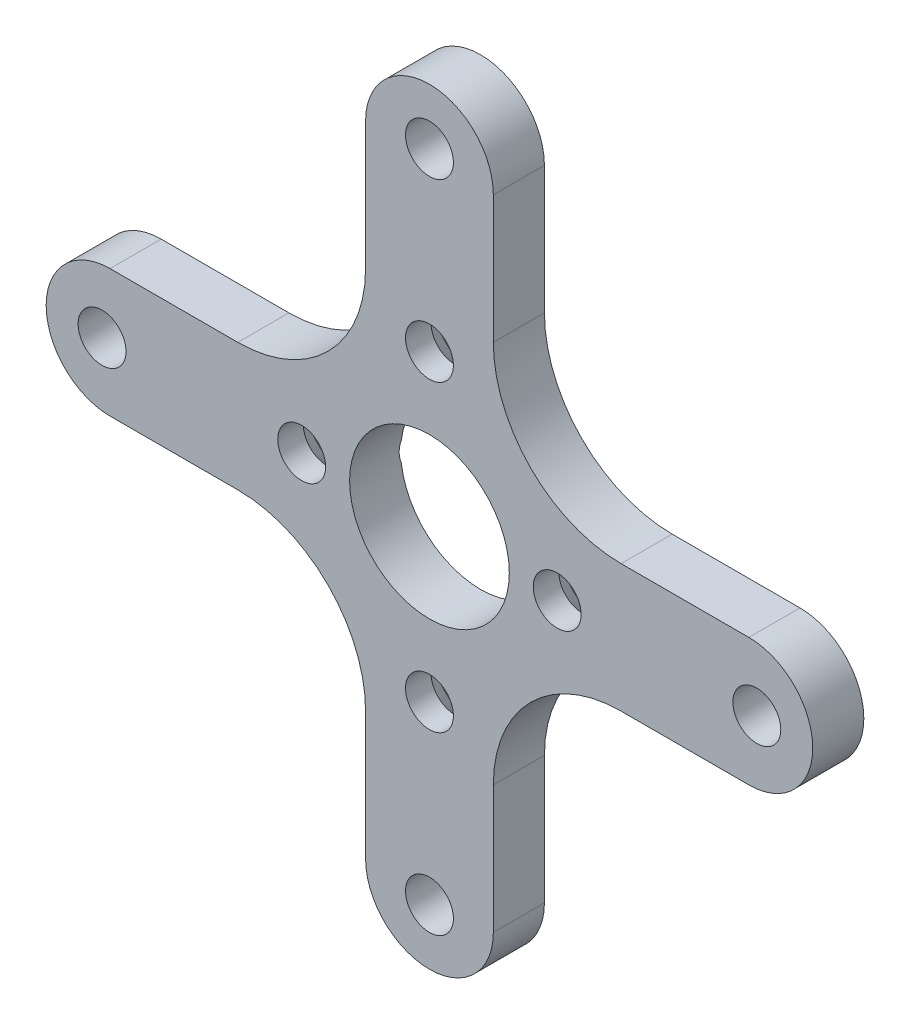
SolidWorks part; units mm, degrees
ref_plane "Спереди" through (0, 0, 0) normal (0, 0, 1) x (1, 0, 0)
ref_plane "Сверху" through (0, 0, 0) normal (0, 1, 0) x (1, 0, 0)
ref_plane "Справа" through (0, 0, 0) normal (1, 0, 0) x (0, 0, -1)
sketch "Эскиз1" plane through (0, 0, 0) normal (0, 0, 1) x (1, 0, 0)
  line L0 (-4, 20) -> (-4, 12)
  line L1 (-12, 4) -> (-20, 4)
  line L2 (-20, -4) -> (-12, -4)
  line L3 (-4, -12) -> (-4, -20)
  line L4 (4, -20) -> (4, -12)
  line L5 (12, -4) -> (20, -4)
  line L6 (4, 20) -> (4, 12)
  line L7 (12, 4) -> (20, 4)
  arc A0 (-4, 20) -> (4, 20) centre (0, 20) cw
  arc A1 (-4, 12) -> (-12, 4) centre (-12, 12) cw
  arc A2 (-20, 4) -> (-20, -4) centre (-20, 0) ccw
  arc A4 (-4, -20) -> (4, -20) centre (0, -20) ccw
  arc A5 (4, -12) -> (12, -4) centre (12, -12) cw
  arc A6 (4, 12) -> (12, 4) centre (12, 12) ccw
  arc A7 (20, 4) -> (20, -4) centre (20, 0) cw
  arc A8 (-12, -4) -> (-4, -12) centre (-12, -12) cw
  circle A13 centre (0, 0) radius 5
  circle A14 centre (0, 0) radius 8 construction
  circle A15 centre (0, 0) radius 9.5 construction
  circle A16 centre (0, 9.5) radius 1.5
  circle A17 centre (0, -9.5) radius 1.5
  circle A18 centre (-8, 0) radius 1.5
  circle A19 centre (8, 0) radius 1.5
  circle A20 centre (0, 0) radius 24 construction
  circle A22 centre (0, 20.5) radius 1.5
  circle A23 centre (20.5, 0) radius 1.5
  circle A24 centre (-20.5, 0) radius 1.5
  circle A25 centre (0, -20.5) radius 1.5
  circle A26 centre (0, 0) radius 20.5 construction
  dimension "D2" = 3
  dimension "D3" = 10
  dimension "D4" = 16
  dimension "D5" = 19
  dimension "D6" = 48
  dimension "D7" = 41
  dimension "D8" = 8
  dimension "D1" = 8
extrude "Бобышка-Вытянуть1" add sketch "Эскиз1" along normal blind 3.2
chamfer "Фаска1" distance 1.6 angle 45 4 edges at (1.5, -9.5, 0) (1.5, 9.5, 0) (-6.5, 0, 0) (9.5, 0, 0)
